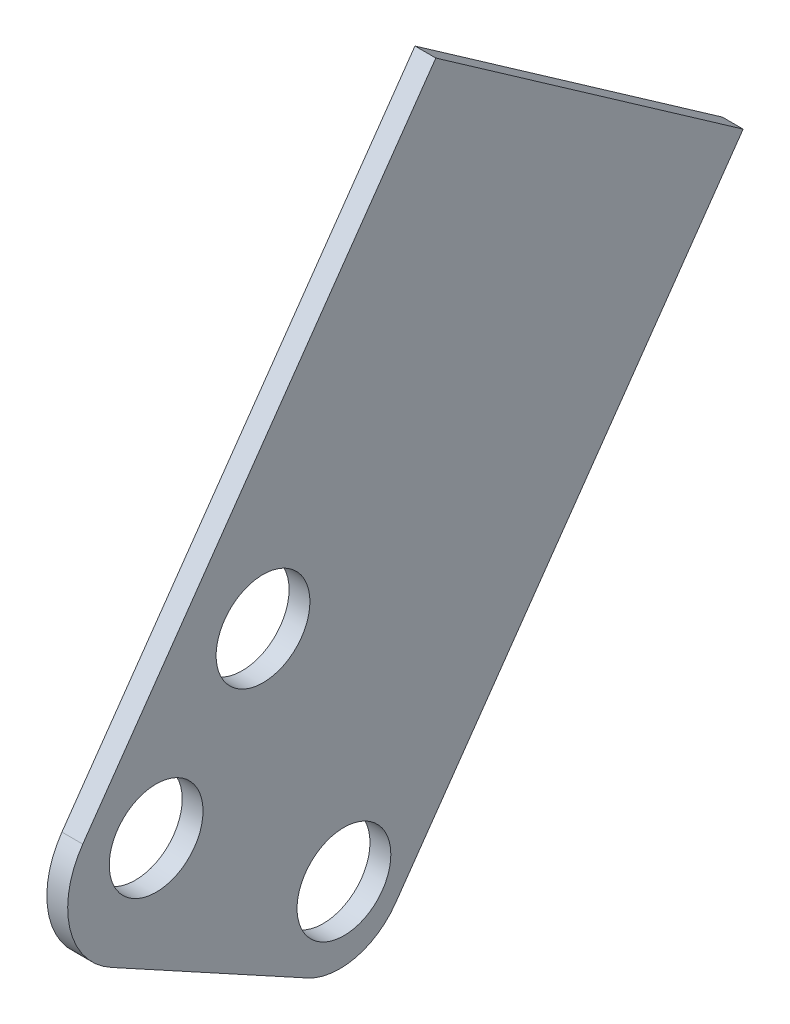
SolidWorks part; units mm, degrees
ref_plane "Front Plane" through (0, 0, 0) normal (0, 0, 1) x (1, 0, 0)
ref_plane "Top Plane" through (0, 0, 0) normal (0, 1, 0) x (1, 0, 0)
ref_plane "Right Plane" through (0, 0, 0) normal (1, 0, 0) x (0, 0, -1)
sketch "Sketch1" plane through (0, 0, 0) normal (1, 0, 0) x (0, 0, -1)
  line L0 (10.5948, 15.1309) -> (116.5507, 166.4517)
  line L1 (17.4625, 0) -> (-17.4625, 0) construction
  line L2 (116.5507, 166.4517) -> (22.9217, 232.0115)
  line L3 (22.9217, 232.0115) -> (-84.6362, 78.4029)
  line L4 (-76.0118, 41.546) -> (-16.2084, 8.8591)
  circle A0 centre (-62.2858, 68.8067) radius 14.2875
  circle A1 centre (-5.0681, 28.7424) radius 14.2875
  arc A2 (10.5948, 15.1309) -> (-16.2084, 8.8591) centre (-6.3105, 26.9681) cw
  arc A3 (-76.0118, 41.546) -> (-84.6362, 78.4029) centre (-63.8298, 63.834) cw
  circle A4 centre (-29.7169, 107.7927) radius 14.2875
  point P13 (0, 0)
  point P16 (-100.9135, 55.1566)
  dimension "D3" = 69.85
  dimension "D8" = 28.575
  dimension "D10" = 20.6375
  dimension "D11" = 25.4
  dimension "D12" = 82.804
  dimension "D13" = 28.575
  dimension "D1" = 203.2
  dimension "D2" = 55
  dimension "D4" = 182.5625
  dimension "D5" = 20.6375
  dimension "D6" = 215.9
  dimension "D7" = 182.5625
  dimension "D9" = 114.3
  dimension "D14" = 50.8
extrude "Boss-Extrude2" add sketch "Sketch1" along normal blind 3.175 and the other way blind 3.175
